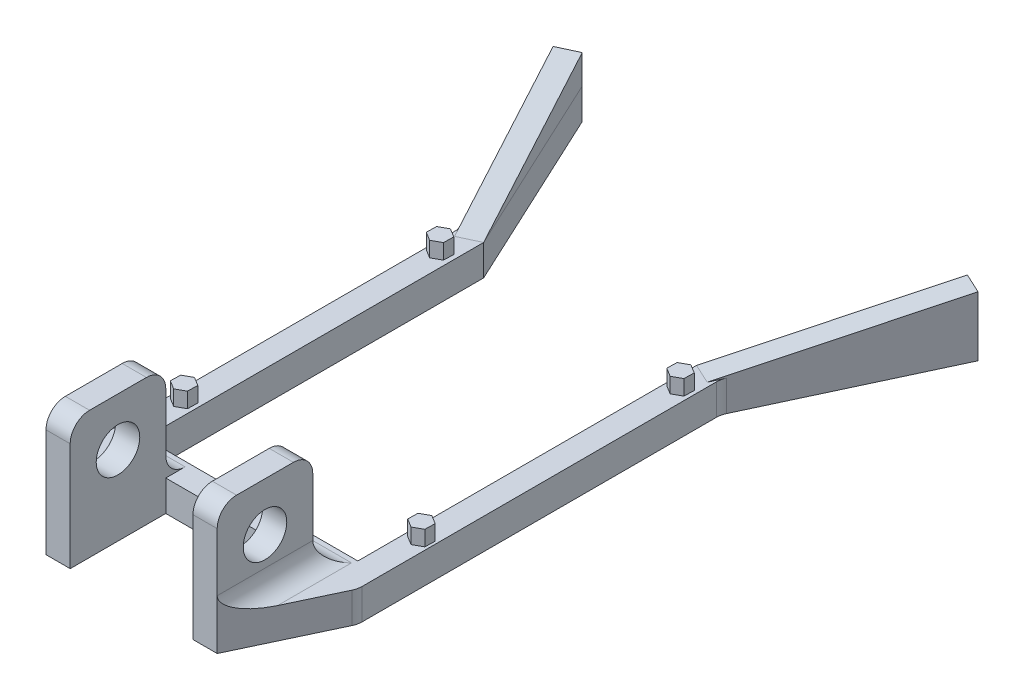
SolidWorks part; units mm, degrees
ref_plane "Front Plane" through (0, 0, 0) normal (0, 0, 1) x (1, 0, 0)
ref_plane "Top Plane" through (0, 0, 0) normal (0, 1, 0) x (1, 0, 0)
ref_plane "Right Plane" through (0, 0, 0) normal (1, 0, 0) x (0, 0, -1)
sketch "Sketch1" plane through (0, 0, 0) normal (0, 1, 0) x (1, 0, 0)
  line L0 (0, -55) -> (0, 55) construction
  line L12 (11, 0) -> (11, 35)
  line L15 (-11, 0) -> (-11, 35)
  line L16 (-11, 0) -> (11, 0)
  line L17 (-13.5, 35) -> (-13.5, -2.5)
  line L18 (13.5, -2.5) -> (13.5, 35)
  line L19 (-11, 35) -> (-19.8989, 54.0837)
  line L20 (-19.8989, 54.0837) -> (-21.9524, 53.1262)
  line L21 (-21.9524, 53.1262) -> (-13.5, 35)
  line L22 (19.8989, 54.0837) -> (21.9524, 53.1262)
  line L23 (21.9524, 53.1262) -> (13.5, 35)
  line L24 (11, 35) -> (19.8989, 54.0837)
  line L25 (6.3445, -2.5) -> (6.3445, -12.3752)
  line L26 (6.3445, -12.3752) -> (8.8445, -12.3752)
  line L29 (-6.3445, -2.5) -> (-6.3445, -12.3752)
  line L30 (-6.3445, -12.3752) -> (-8.8445, -12.3752)
  line L32 (-6.3445, -2.5) -> (6.3445, -2.5)
  line L33 (8.8445, -12.3752) -> (13.5, -2.5)
  line L34 (-13.5, -2.5) -> (-8.8445, -12.3752)
  line L35 (13.0991, 31.5894) -> (13.1252, 32.6359)
  line L36 (-11.4924, 31.3342) -> (-11.4662, 32.3807)
  line L37 (-11.4662, 32.3807) -> (-12.3595, 32.9265)
  line L38 (-12.3595, 32.9265) -> (-13.2788, 32.4259)
  line L39 (-13.2788, 32.4259) -> (-13.305, 31.3794)
  line L40 (-13.305, 31.3794) -> (-12.4117, 30.8335)
  line L41 (-12.4117, 30.8335) -> (-11.4924, 31.3342)
  line L42 (13.1252, 32.6359) -> (12.232, 33.1818)
  line L43 (12.232, 33.1818) -> (11.3126, 32.6812)
  line L44 (11.3126, 32.6812) -> (11.2865, 31.6347)
  line L45 (11.2865, 31.6347) -> (12.1797, 31.0888)
  line L46 (12.1797, 31.0888) -> (13.0991, 31.5894)
  line L47 (-11.4217, 4.8146) -> (-11.3955, 5.8611)
  line L48 (-11.3955, 5.8611) -> (-12.2888, 6.4069)
  line L49 (-12.2888, 6.4069) -> (-13.2081, 5.9063)
  line L50 (-13.2081, 5.9063) -> (-13.2343, 4.8598)
  line L51 (-13.2343, 4.8598) -> (-12.341, 4.3139)
  line L52 (-12.341, 4.3139) -> (-11.4217, 4.8146)
  line L53 (13.203, 4.7152) -> (13.2291, 5.7617)
  line L54 (13.2291, 5.7617) -> (12.3359, 6.3076)
  line L55 (12.3359, 6.3076) -> (11.4165, 5.8069)
  line L56 (11.4165, 5.8069) -> (11.3904, 4.7604)
  line L57 (11.3904, 4.7604) -> (12.2837, 4.2145)
  line L58 (12.2837, 4.2145) -> (13.203, 4.7152)
  circle A0 centre (-12.3856, 31.88) radius 0.9066 construction
  point P0 (0, 0)
  dimension "D1" = 22
  dimension "D3" = 2.5
  dimension "D4" = 20
  dimension "D5" = 155
  dimension "D6" = 35
  dimension "D7" = 2.5
extrude "Boss-Extrude1" add sketch "Sketch1" along normal blind 3.175
sketch "Sketch2" plane through (4.3704, 0, -2.038) normal (0.9063, 0, -0.4226) x (-0.4226, 0, -0.9063)
  line L0 (36.3696, 3.175) -> (57.4261, 6.175)
  line L1 (57.4261, 6.175) -> (57.4261, 3.175)
  line L2 (36.3696, 3.175) -> (57.4261, 3.175) construction
  line L3 (36.3696, 3.175) -> (57.4261, 3.175)
  dimension "D1" = 3
extrude "Boss-Extrude2" add sketch "Sketch2" against normal up to surface (2.2658 mm away) separate body up to face at (-17.7262, 1.5875, -44.0631)
mirror "Mirror4" about plane through (0, 0, 0) normal (1, 0, 0) of "Boss-Extrude2"
sketch "Sketch3" plane through (0, 3.175, 0) normal (0, 1, 0) x (1, 0, 0)
  line L0 (-6.3445, -2.5) -> (6.3445, -2.5) construction
  line L23 (6.3445, -12.3752) -> (8.8445, -12.3752) construction
  line L24 (8.8445, -12.3752) -> (6.3445, -12.3752)
  line L25 (8.8445, -12.3752) -> (8.8445, -2.5)
  line L26 (8.8445, -2.5) -> (6.3445, -2.5)
  line L27 (6.3445, -12.3752) -> (6.3445, -2.5)
  line L28 (6.3445, -2.5) -> (6.3445, -12.3752) construction
  line L29 (0, -55) -> (0, 55) construction
  line L30 (-8.8445, -2.5) -> (-6.3445, -2.5)
  line L31 (-6.3445, -12.3752) -> (-6.3445, -2.5)
  line L32 (-8.8445, -12.3752) -> (-6.3445, -12.3752)
  line L33 (-8.8445, -12.3752) -> (-8.8445, -2.5)
  line L34 (-13.5, -2.5) -> (-8.8445, -12.3752) construction
  line L35 (-8.8445, -12.3752) -> (-6.3445, -12.3752) construction
extrude "Boss-Extrude3" add sketch "Sketch3" along normal blind 10
sketch "Sketch4" plane through (8.8445, 0, 0) normal (1, 0, 0) x (0, 0, -1)
  line L0 (-12.3752, 13.175) -> (-2.5, 13.175) construction
  line L1 (-2.5, 13.175) -> (-2.5, 3.175) construction
  circle A0 centre (-7.4376, 8.175) radius 2.25
  point P5 (-7.4376, 13.175)
  point P8 (-2.5, 8.175)
  dimension "D1" = 4.5
fillet "Fillet1" radius 2 12 edges at (-8.8445, 3.175, 7.4376) (8.8445, 3.175, 7.4376) (7.5945, 3.175, 2.5) (-7.5945, 3.175, 2.5) (13.5, 1.5875, -35) (13.5, 1.5875, 2.5) (-13.5, 1.5875, -35) (-13.5, 1.5875, 2.5) (7.5945, 13.175, 12.3752) (7.5945, 13.175, 2.5) (-7.5945, 13.175, 2.5) (-7.5945, 13.175, 12.3752)
extrude "Boss-Extrude4" add sketch "Sketch1<4>" along normal blind 4.75 contours L40 L41 L36 L37 L38 L39 | L45 L46 L35 L42 L43 L44 | L47 L48 L49 L50 L51 L52 | L53 L54 L55 L56 L57 L58 region at (12.2058, 0, -32.1353) region at (-12.3856, 0, -31.88)
sketch "Sketch1<4>" plane through (0, 0, 0) normal (0, 1, 0) x (1, 0, 0) same geometry as "Sketch1"
extrude "Cut-Extrude1" cut sketch "Sketch4" against normal blind 18.5 contours A0
